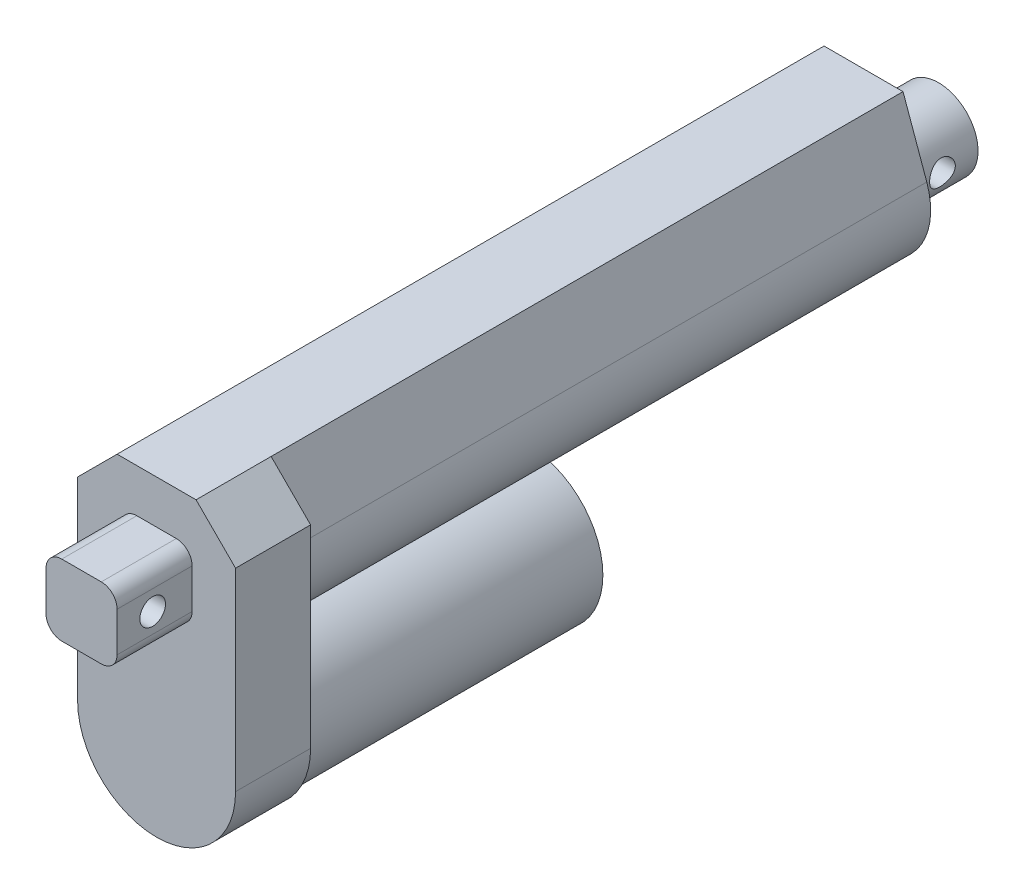
SolidWorks part; units mm, degrees
ref_plane "정면" through (0, 0, 0) normal (0, 0, 1) x (1, 0, 0)
ref_plane "윗면" through (0, 0, 0) normal (0, 1, 0) x (1, 0, 0)
ref_plane "우측면" through (0, 0, 0) normal (1, 0, 0) x (0, 0, -1)
sketch "스케치1" plane through (0, 0, 0) normal (0, 0, 1) x (1, 0, 0)
  line L0 (-20, 0) -> (-20, 49)
  line L1 (-20, 49) -> (-10, 59)
  line L2 (-10, 59) -> (10, 59)
  line L3 (10, 59) -> (20, 49)
  line L4 (20, 49) -> (20, 0)
  circle A0 centre (0, 0) radius 20
  point P11 (0, 59)
  dimension "D1" = 40
  dimension "D2" = 49
  dimension "D3" = 20
  dimension "D4" = 59
extrude "보스-돌출1" add sketch "스케치1" against normal blind 19 contours A0 L4 L3 L2 L1 L0 | A0 region at (0, 35.9874, 0) region at (0, 0, 0)
sketch "스케치2" plane through (0, 0, -19) normal (0, 0, -1) x (-1, 0, 0)
  line L0 (-10, 59) -> (10, 59)
  line L1 (10, 59) -> (-10, 59) construction
  line L2 (-10, 59) -> (-16.0091, 42.1791)
  line L3 (10, 59) -> (16.0091, 42.1791)
  circle A0 centre (0, 36.46) radius 10
  circle A1 centre (0, 36.46) radius 17
  point P4 (0, 59)
  line M3 (10, 59) -> (-10, 59)
  dimension "D1" = 36.46
  dimension "D2" = 20
  dimension "D3" = 34
  dimension "D4" = 20
extrude "보스-돌출2" add sketch "스케치2" along normal blind 160 contours A1 L3 L2 M3 | A1 A0 | A0 region at (0, 54.6113, -19) region at (0, 52.9792, -19) region at (0, 36.46, -19)
extrude "보스-돌출3" add sketch "스케치2<3>" along normal blind 19 from offset 160 contours A0
sketch "스케치2<3>" plane through (0, 0, -19) normal (0, 0, -1) x (-1, 0, 0) same geometry as "스케치2"
sketch "스케치3" plane through (0, 0, 0) normal (1, 0, 0) x (0, 0, -1)
  circle A0 centre (189, 36) radius 3.25
  dimension "D1" = 6.5
  dimension "D2" = 189
  dimension "D3" = 36
extrude "컷-돌출1" cut sketch "스케치3" against normal through all both and the other way through all
sketch "스케치4" plane through (0, 0, -19) normal (0, 0, -1) x (-1, 0, 0)
  circle A0 centre (0, 0) radius 19
  dimension "D1" = 38
extrude "보스-돌출4" add sketch "스케치4" along normal blind 75
sketch "스케치5" plane through (0, 0, 0) normal (0, 0, 1) x (1, 0, 0)
  line L1 (-9, 48) -> (9, 48)
  line L2 (-9, 48) -> (-9, 30)
  line L3 (-9, 30) -> (9, 30)
  line L4 (9, 48) -> (9, 30)
  line L5 (-9, 48) -> (9, 30) construction
  line L6 (-9, 30) -> (9, 48) construction
  point P0 (0, 39)
  dimension "D1" = 30
  dimension "D2" = 18
  dimension "D3" = 18
extrude "보스-돌출5" add sketch "스케치5" along normal blind 19
fillet "필렛1" radius 4 4 edges at (-9, 30, 9.5) (9, 30, 9.5) (-9, 48, 9.5) (9, 48, 9.5)
sketch "스케치6" plane through (-9, 0, 0) normal (-1, 0, 0) x (0, 0, 1)
  line L0 (19, 44) -> (19, 34) construction
  circle A0 centre (10, 39) radius 3.25
  point P5 (19, 39)
  dimension "D1" = 6.5
  dimension "D2" = 9
extrude "컷-돌출2" cut sketch "스케치6" against normal through all
